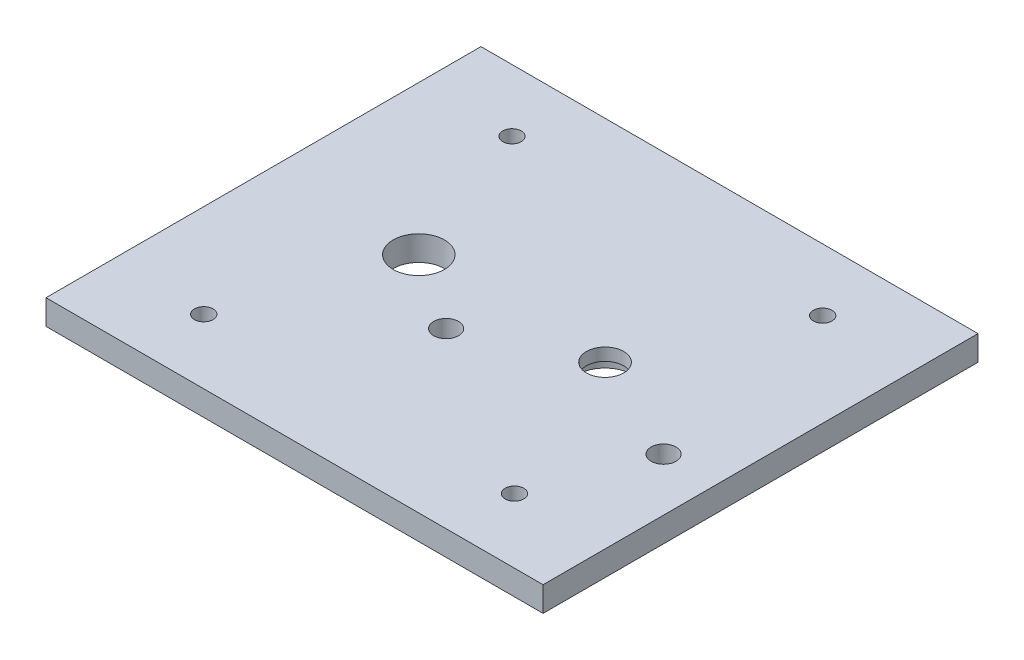
SolidWorks part; units mm, degrees
ref_plane "Front Plane" through (0, 0, 0) normal (0, 0, 1) x (1, 0, 0)
ref_plane "Top Plane" through (0, 0, 0) normal (0, 1, 0) x (1, 0, 0)
ref_plane "Right Plane" through (0, 0, 0) normal (1, 0, 0) x (0, 0, -1)
sketch "Sketch1" plane through (0, 0, 0) normal (0, 1, 0) x (1, 0, 0)
  line L0 (0, 8.2993) -> (0, -7.906) construction
  line L1 (-40, 35) -> (40, 35)
  line L2 (-40, 35) -> (-40, -35)
  line L3 (-40, -35) -> (40, -35)
  line L4 (40, 35) -> (40, -35)
  line L5 (-40, 35) -> (40, -35) construction
  line L6 (-40, -35) -> (40, 35) construction
  line L7 (-14.9915, 0.1967) -> (11.9413, 0.1967) construction
  line L9 (35.0085, 0.1967) -> (61.9413, 0.1967) construction
  line L11 (12.5001, 2.9838) -> (12.5001, -1.0162)
  line L13 (15.4999, 3.0162) -> (15.4999, -0.9838)
  line L14 (12.5001, 2.9838) -> (15.4999, -0.9838) construction
  line L15 (12.5001, -1.0162) -> (15.4999, 3.0162) construction
  circle A0 centre (-25, 25) radius 1.5
  circle A1 centre (25, 25) radius 1.5
  circle A2 centre (25, -24.6067) radius 1.5
  circle A3 centre (-25, -24.6067) radius 1.5
  circle A4 centre (14, 1) radius 10
  circle A5 centre (-16, 1) radius 20
  arc A6 (12.5001, 2.9838) -> (15.4999, 3.0162) centre (14.0217, 1.0001) cw
  arc A7 (12.5001, -1.0162) -> (15.4999, -0.9838) centre (13.9783, 0.9999) ccw
  circle A8 centre (13.9783, 0.9999) radius 4.5
  circle A9 centre (14, -6) radius 14
  circle A10 centre (-3.5, -7.1027) radius 2
  circle A11 centre (31.5, -7.1027) radius 2
  circle A12 centre (-16, 1) radius 4.125
  circle A13 centre (13.9783, 0.9999) radius 3
  point P0 (0, 0)
  dimension "D3" = 15
  dimension "D6" = 3
  dimension "D7" = 26
  dimension "D10" = 20
  dimension "D11" = 9
  dimension "D12" = 7
  dimension "D13" = 17.5
  dimension "D14" = 4
  dimension "D15" = 4
  dimension "D17" = 40
  dimension "D20" = 8.25
  dimension "D21" = 6
  dimension "D1" = 80
  dimension "D2" = 70
  dimension "D4" = 10
  dimension "D8" = 4
  dimension "D9" = 3
  dimension "D16" = 17.5
  dimension "D18" = 36
  dimension "D19" = 4
  dimension "D5" = 2
extrude "Boss-Extrude4" add sketch "Sketch1" along normal blind 4 contours L4 L1 L2 L3 A11 A9 A4 A5 A2 A1 A0 A3 | A9 A5 A10 | A9 A4 | A5 A9 A4 | A5 A9 | A4 A9 A8 | A8 A13 | A4 A9 A5 region at (0, 0, -33.937) region at (4.4048, 0, -2.6588) region at (4.1111, 0, -3.2378) region at (1.9776, 0, 3.1948) region at (15.1814, 0, 11.2492) region at (14, 0, -8.4705) region at (-0.1835, 0, 2.6905) region at (9.6056, 0, -0.9999)
sketch "Sketch2" plane through (0, 4, 0) normal (0, 1, 0) x (1, 0, 0)
  circle A3 centre (-16, 1) radius 9.125
  circle A4 centre (-16, 1) radius 9.125
  dimension "D1" = 5
extrude "Cut-Extrude2" cut sketch "Sketch1<7>" along normal blind 2 contours A8
sketch "Sketch1<7>" plane through (0, 0, 0) normal (0, 1, 0) x (1, 0, 0) same geometry as "Sketch1"
